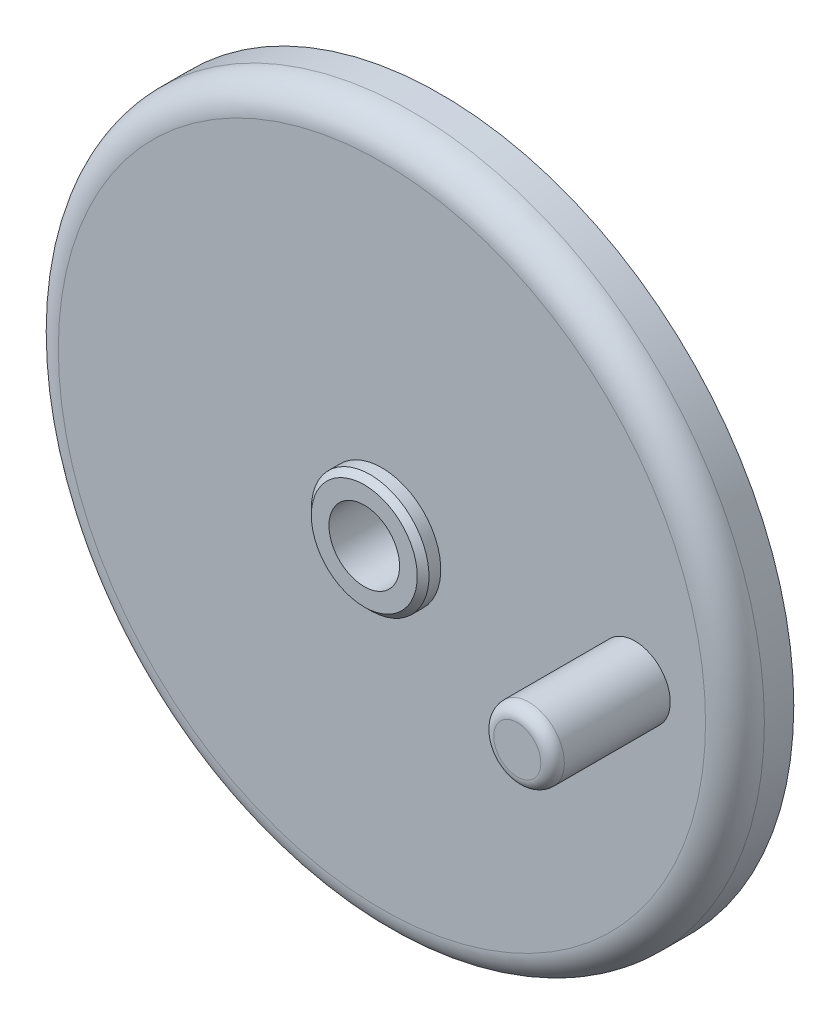
SolidWorks part; units mm, degrees
ref_plane "Front Plane" through (0, 0, 0) normal (0, 0, 1) x (1, 0, 0)
ref_plane "Top Plane" through (0, 0, 0) normal (0, 1, 0) x (1, 0, 0)
ref_plane "Right Plane" through (0, 0, 0) normal (1, 0, 0) x (0, 0, -1)
sketch "Sketch1" plane through (0, 0, 0) normal (0, 0, 1) x (1, 0, 0)
  circle A0 centre (0, 0) radius 60
  dimension "D1" = 120
extrude "Boss-Extrude1" add sketch "Sketch1" along normal blind 10
fillet "Fillet1" radius 5 1 edges at (60, 0, 10)
sketch "Sketch2" plane through (0, 0, 0) normal (0, 0, 1) x (1, 0, 0)
  circle A0 centre (0, 0) radius 10
  circle A1 centre (0, 0) radius 6
  dimension "D1" = 20
  dimension "D2" = 12
extrude "Boss-Extrude3" add sketch "Sketch2" along normal blind 13 contours A0
extrude "Cut-Extrude1" cut sketch "Sketch2<3>" along normal through all contours A1
sketch "Sketch2<3>" plane through (0, 0, 0) normal (0, 0, 1) x (1, 0, 0) same geometry as "Sketch2"
chamfer "Chamfer1" distance 1 angle 45 1 edges at (10, 0, 13)
sketch "Sketch3" plane through (0, 0, 0) normal (0, 0, 1) x (1, 0, 0)
  circle A0 centre (43, 0) radius 6
  dimension "D2" = 12
  dimension "D1" = 43
extrude "Boss-Extrude4" add sketch "Sketch3" along normal blind 30
fillet "Fillet2" radius 2 1 edges at (49, 0, 30)
